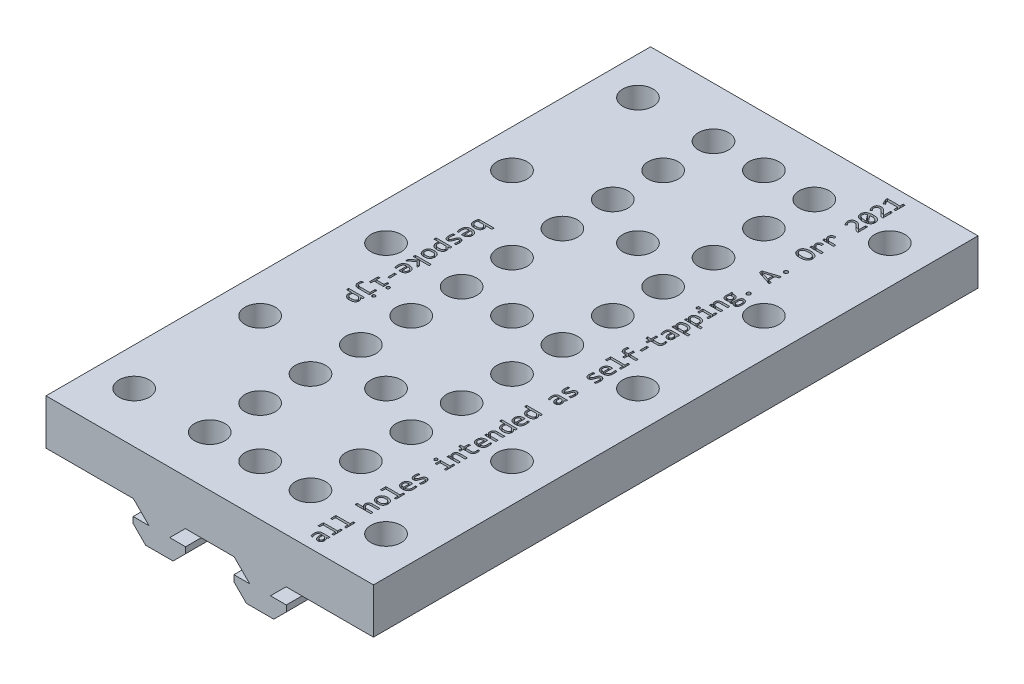
SolidWorks part; units mm, degrees
ref_plane "Front Plane" through (0, 0, 0) normal (0, 0, 1) x (1, 0, 0)
ref_plane "Top Plane" through (0, 0, 0) normal (0, 1, 0) x (1, 0, 0)
ref_plane "Right Plane" through (0, 0, 0) normal (1, 0, 0) x (0, 0, -1)
sketch "Sketch1" plane through (0, 0, 0) normal (0, 0, 1) x (1, 0, 0)
  line L0 (-3.3729, 41.999) -> (-1.5729, 40.199)
  line L1 (-21.2929, 51.999) -> (43.7071, 51.999)
  line L2 (-21.2929, 51.999) -> (-21.2929, 41.999)
  line L3 (-21.2929, 41.999) -> (-3.3729, 41.999)
  line L4 (43.7071, 51.999) -> (43.7071, 41.999)
  line L5 (-1.5729, 40.199) -> (-4.2929, 40.199)
  line L6 (-4.2929, 40.199) -> (-4.2929, 38.559)
  line L7 (-4.2929, 38.559) -> (-1.6329, 35.899)
  line L8 (-1.6329, 35.899) -> (4.0471, 35.899)
  line L9 (1.2071, 35.899) -> (1.2071, 41.999) construction
  line L10 (6.7071, 38.559) -> (4.0471, 35.899)
  line L11 (6.7071, 40.199) -> (6.7071, 38.559)
  line L12 (3.9871, 40.199) -> (6.7071, 40.199)
  line L13 (5.7871, 41.999) -> (3.9871, 40.199)
  line L14 (11.2071, 103.2482) -> (11.2071, 0.7497) construction
  line L15 (21.2071, 35.899) -> (21.2071, 41.999) construction
  line L16 (16.6271, 41.999) -> (18.4271, 40.199)
  line L17 (18.4271, 40.199) -> (15.7071, 40.199)
  line L18 (15.7071, 40.199) -> (15.7071, 38.559)
  line L19 (15.7071, 38.559) -> (18.3671, 35.899)
  line L20 (24.0471, 35.899) -> (18.3671, 35.899)
  line L21 (26.7071, 38.559) -> (24.0471, 35.899)
  line L22 (26.7071, 40.199) -> (26.7071, 38.559)
  line L23 (23.9871, 40.199) -> (26.7071, 40.199)
  line L24 (25.7871, 41.999) -> (23.9871, 40.199)
  line L25 (5.7871, 41.999) -> (16.6271, 41.999)
  line L26 (25.7871, 41.999) -> (43.7071, 41.999)
  point P31 (11.2071, 51.999)
  dimension "D1" = 5.42
  dimension "D2" = 10
  dimension "D3" = 45
  dimension "D4" = 65
  dimension "D5" = 1.8
  dimension "D6" = 4.3
  dimension "D7" = 10
  dimension "D8" = 1.64
  dimension "D9" = 4.5
extrude "Boss-Extrude1" add sketch "Sketch1" along normal blind 120
other "Move Face1" flip direction yes face at (25.3471, 40.199, 60) face at (24.8871, 41.099, 60) face at (26.7071, 39.379, 60) face at (25.3771, 37.229, 60) face at (21.2071, 35.899, 60) face at (15.7071, 39.379, 60) face at (17.0671, 40.199, 60) face at (17.0371, 37.229, 60) face at (17.5271, 41.099, 60) face at (4.8871, 41.099, 60) face at (5.3471, 40.199, 60) face at (6.7071, 39.379, 60) face at (5.3771, 37.229, 60) face at (1.2071, 35.899, 60) face at (-2.9629, 37.229, 60) face at (-4.2929, 39.379, 60) face at (-2.9329, 40.199, 60) face at (-2.4729, 41.099, 60) offset 0.3 parameters "D1"=0.3
other "Move Face2" flip direction yes face at (11.2071, 41.999, 60) face at (-12.1208, 41.999, 60) face at (34.535, 41.999, 60) offset 1 parameters "D1"=1
sketch "Sketch2" plane through (0, 51.999, 0) normal (0, 1, 0) x (1, 0, 0)
  line L0 (43.7071, -120) -> (-21.2929, -120) construction
  line L2 (43.7071, -120) -> (43.7071, 0) construction
  circle A0 centre (36.2071, -110) radius 3
  circle A1 centre (36.2071, -85) radius 3
  circle A2 centre (36.2071, -60) radius 3
  circle A3 centre (36.2071, -35) radius 3
  circle A4 centre (36.2071, -10) radius 3
  circle A5 centre (11.2071, -85) radius 3
  circle A6 centre (11.2071, -60) radius 3
  circle A7 centre (11.2071, -35) radius 3
  circle A8 centre (11.2071, -10) radius 3
  circle A9 centre (-13.7929, -85) radius 3
  circle A10 centre (-13.7929, -60) radius 3
  circle A11 centre (-13.7929, -35) radius 3
  circle A12 centre (-13.7929, -10) radius 3
  circle A13 centre (11.2071, -110) radius 3
  circle A14 centre (-13.7929, -110) radius 3
  point P35 (11.2071, -120)
  point P37 (43.7071, -60)
  dimension "D1" = 6
  dimension "D2" = 5
  dimension "D3" = 3
extrude "Cut-Extrude1" cut sketch "Sketch2" against normal up to surface (9 mm away) up to face at (-12.6208, 42.999, 60)
sketch "Sketch3" plane through (0, 36.199, 0) normal (0, -1, 0) x (1, 0, 0)
  line L0 (-1.5086, 120) -> (3.9228, 120) construction
  line L1 (11.2071, 0) -> (11.2071, 120) construction
  line L2 (6.3628, 0) -> (16.0514, 0) construction
  line L3 (6.3628, 120) -> (16.0514, 120) construction
  line L5 (-1.5086, 60) -> (3.9228, 60) construction
  line L6 (-1.5086, 120) -> (-1.5086, 0) construction
  line L7 (3.9228, 120) -> (3.9228, 0) construction
  circle A0 centre (1.2071, 110) radius 1.5
  circle A1 centre (1.2071, 100) radius 1.5
  circle A2 centre (1.2071, 90) radius 1.5
  circle A3 centre (1.2071, 80) radius 1.5
  circle A4 centre (1.2071, 70) radius 1.5
  circle A5 centre (1.2071, 60) radius 1.5
  circle A6 centre (1.2071, 50) radius 1.5
  circle A7 centre (1.2071, 40) radius 1.5
  circle A8 centre (1.2071, 30) radius 1.5
  circle A9 centre (1.2071, 20) radius 1.5
  circle A10 centre (1.2071, 10) radius 1.5
  circle A11 centre (21.2071, 110) radius 1.5
  circle A12 centre (21.2071, 100) radius 1.5
  circle A13 centre (21.2071, 90) radius 1.5
  circle A14 centre (21.2071, 80) radius 1.5
  circle A15 centre (21.2071, 70) radius 1.5
  circle A16 centre (21.2071, 60) radius 1.5
  circle A17 centre (21.2071, 50) radius 1.5
  circle A18 centre (21.2071, 40) radius 1.5
  circle A19 centre (21.2071, 30) radius 1.5
  circle A20 centre (21.2071, 20) radius 1.5
  circle A21 centre (21.2071, 10) radius 1.5
  point P5 (1.2071, 120)
  point P59 (1.2071, 60)
  dimension "D1" = 3
  dimension "D2" = 11
extrude "Cut-Extrude2" cut sketch "Sketch3" against normal through all
sketch "Sketch5" plane through (0, 51.999, 0) normal (0, 1, 0) x (1, 0, 0)
  line L0 (31.2071, -120) -> (31.2071, 0) construction
  line L1 (43.7071, -120) -> (-21.2929, -120) construction
  line L2 (43.7071, 0) -> (-21.2929, 0) construction
  line L3 (11.2071, -120) -> (11.2071, 0) construction
  line L4 (-8.7929, -120) -> (-8.7929, 0) construction
  circle A0 centre (36.2071, -35) radius 3 construction
  text T0 "all holes intended as self-tapping. A. Orr 2021" font "Consolas" height 2.9
  text T1 "bespoke-ijp" font "Consolas" height 2.9
  dimension "D1" = 5
extrude "Cut-Extrude7" cut sketch "Sketch5" against normal blind 1
sketch "Sketch6" plane through (0, 51.999, 0) normal (0, 1, 0) x (1, 0, 0)
  line L1 (11.2071, -120) -> (11.2071, 0) construction
  line L2 (43.7071, -120) -> (-21.2929, -120) construction
  line L3 (43.7071, 0) -> (-21.2929, 0) construction
  circle A0 centre (21.2071, -110) radius 3
  circle A1 centre (21.2071, -100) radius 3
  circle A2 centre (21.2071, -90) radius 3
  circle A3 centre (21.2071, -80) radius 3
  circle A4 centre (21.2071, -70) radius 3
  circle A5 centre (21.2071, -60) radius 3
  circle A6 centre (21.2071, -50) radius 3
  circle A7 centre (21.2071, -40) radius 3
  circle A8 centre (21.2071, -30) radius 3
  circle A9 centre (21.2071, -20) radius 3
  circle A10 centre (21.2071, -10) radius 3
  circle A11 centre (1.2071, -10) radius 3
  circle A12 centre (1.2071, -20) radius 3
  circle A13 centre (1.2071, -30) radius 3
  circle A14 centre (1.2071, -40) radius 3
  circle A15 centre (1.2071, -50) radius 3
  circle A16 centre (1.2071, -60) radius 3
  circle A17 centre (1.2071, -70) radius 3
  circle A18 centre (1.2071, -80) radius 3
  circle A19 centre (1.2071, -90) radius 3
  circle A20 centre (1.2071, -100) radius 3
  circle A21 centre (1.2071, -110) radius 3
  dimension "D1" = 6
  dimension "D2" = 11
extrude "Cut-Extrude8" cut sketch "Sketch6" against normal blind 5
